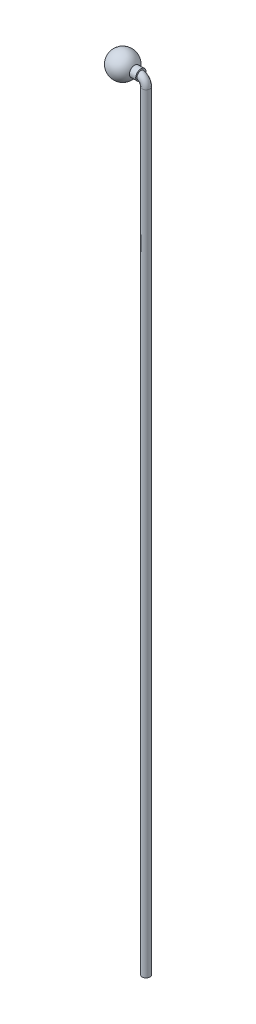
SolidWorks part; units mm, degrees
ref_plane "Front Plane" through (0, 0, 0) normal (0, 0, 1) x (1, 0, 0)
ref_plane "Top Plane" through (0, 0, 0) normal (0, 1, 0) x (1, 0, 0)
ref_plane "Right Plane" through (0, 0, 0) normal (1, 0, 0) x (0, 0, -1)
sketch "Sketch1" plane through (0, 0, 0) normal (1, 0, 0) x (0, 0, -1)
  line L0 (0, 0.165) -> (0, -0.165) construction
  circle A0 centre (0, 0) radius 0.15
  dimension "D1" = 0.3
sketch "Sketch3" plane through (0, 0, 0) normal (0, 0, 1) x (1, 0, 0)
  line L0 (0, 0) -> (0.6, 0)
  line L1 (0.9, -0.3) -> (0.9, -30)
  arc A0 (0.9, -0.3) -> (0.6, 0) centre (0.6, -0.3) ccw
  point P6 (0.9, 0)
  dimension "D3" = 0.3
  dimension "D1" = 30
  dimension "D2" = 0.9
sweep "Sweep1" add profiles "Sketch1" path "Sketch3"
sketch "Sketch6" plane through (0, 0, 0) normal (-1, 0, 0) x (0, 0, 1)
  circle A0 centre (0, 0) radius 0.2
  dimension "D1" = 0.4
extrude "Boss-Extrude1" add sketch "Sketch6" against normal blind 0.7
sketch "Sketch4" plane through (0, 0, 0) normal (-1, 0, 0) x (0, 0, 1)
  line L0 (0, 0.5) -> (0, -0.5)
  arc A0 (0, 0.5) -> (0, -0.5) centre (0, 0) ccw
  dimension "D1" = 1
revolve "Revolve2" add sketch "Sketch4" angle 360 about L0
sketch "Sketch5" plane through (0, 0, 0) normal (0, 0, 1) x (1, 0, 0)
  line L0 (0.9, -0.3) -> (0.9, -30) construction
  line L1 (0.9, -0.3) -> (0.9, -30)
